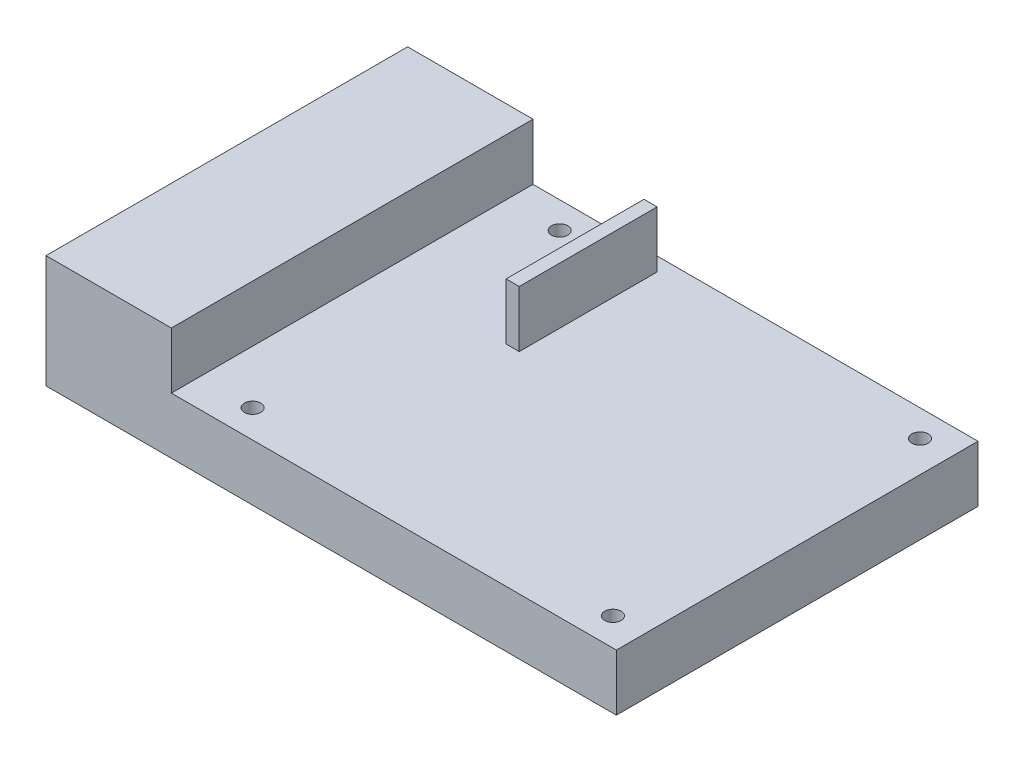
SolidWorks part; units mm, degrees
ref_plane "Front Plane" through (0, 0, 0) normal (0, 0, 1) x (1, 0, 0)
ref_plane "Top Plane" through (0, 0, 0) normal (0, 1, 0) x (1, 0, 0)
ref_plane "Right Plane" through (0, 0, 0) normal (1, 0, 0) x (0, 0, -1)
sketch "Sketch1" plane through (0, 0, 0) normal (0, 1, 0) x (1, 0, 0)
  line L0 (0, 0) -> (0, -57.7)
  line L1 (0, -57.7) -> (91, -57.7)
  line L2 (91, -57.7) -> (91, 0)
  line L3 (91, 0) -> (0, 0)
  line L4 (20, 0) -> (20, -57.7)
  line L5 (39.92, -2.214) -> (39.92, -24.214)
  line L6 (39.92, -24.214) -> (42.0134, -24.214)
  line L7 (42.0134, -24.214) -> (42.0134, -2.214)
  line L8 (42.0134, -2.214) -> (39.92, -2.214)
  circle A0 centre (28.5, -4.2445) radius 1.3
  circle A1 centre (28.5, -53.2445) radius 1.3
  circle A2 centre (86, -53.2445) radius 1.3
  circle A3 centre (86, -4.2445) radius 1.3
  point P19 (63.1648, -51.9567)
  point P20 (0, 0)
  point P21 (0, 0)
  point P22 (0, 0)
  point P23 (0, 0)
  point P24 (0, 0)
  point P25 (0, 0)
  point P26 (3.8939, -53.106)
  point P27 (16.766, -4.2445)
  point P28 (0, 0)
  point P29 (0, -28.85)
  dimension "D1" = 2.6
  dimension "D2" = 57.5
  dimension "D3" = 49
  dimension "D4" = 22
  dimension "D5" = 91
  dimension "D6" = 57.7
  dimension "D7" = 46.08
  dimension "D8" = 5
  dimension "D9" = 20
extrude "Boss-Extrude1" add sketch "Sketch1" along normal blind 18 contours L4 L3 L0 L1 | L8 L5 L6 L7 region at (10, 0, 28.85)
extrude "Boss-Extrude2" add sketch "Sketch1<3>" along normal blind 9 contours L3 L4 L1 L2 A3 A2 A1 A0 L8 L7 L6 L5 region at (55.6569, 0, 29.0293)
sketch "Sketch1<3>" plane through (0, 0, 0) normal (0, 1, 0) x (1, 0, 0) same geometry as "Sketch1"
